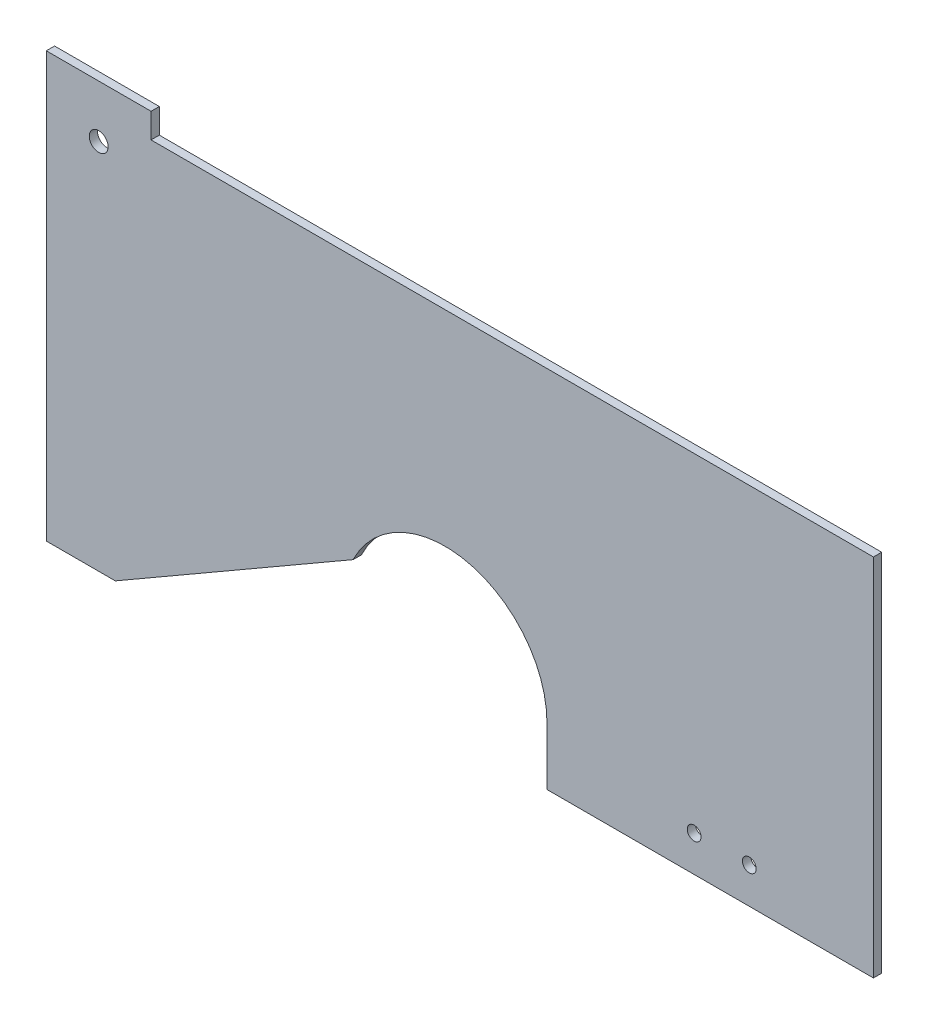
SolidWorks part; units mm, degrees
ref_plane "Front Plane" through (0, 0, 0) normal (0, 0, 1) x (1, 0, 0)
ref_plane "Top Plane" through (0, 0, 0) normal (0, 1, 0) x (1, 0, 0)
ref_plane "Right Plane" through (0, 0, 0) normal (1, 0, 0) x (0, 0, -1)
sketch "Sketch2" plane through (0, 0, 0) normal (0, 0, 1) x (1, 0, 0)
  line L0 (25.0304, 0) -> (111.2865, 49.8)
  line L1 (0, 0) -> (25.0304, 0)
  line L2 (0, 0) -> (0, 154)
  line L4 (300, 0) -> (300, 145)
  line L5 (181.6, 33.7) -> (181.6, 0)
  line L6 (181.6, 0) -> (300, 0)
  line L7 (19, 135) -> (19, 164.3674) construction
  line L11 (38, 145) -> (300, 145)
  line L12 (0, 154) -> (19, 154)
  line L13 (19, 154) -> (38, 154)
  line L14 (38, 154) -> (38, 145)
  line L15 (19, 135) -> (50019, 135) construction
  line L20 (19, 135) -> (19, -49865) construction
  circle A0 centre (19, 135) radius 3.425
  arc A1 (181.6, 33.7) -> (111.2865, 49.8) centre (144.6, 33.7) ccw
  point P19 (19, 154)
  dimension "D3" = 135
  dimension "D4" = 19
  dimension "D5" = 6.85
  dimension "D6" = 74
  dimension "D7" = 155.4
  dimension "D8" = 33.7
  dimension "D1" = 300
  dimension "D2" = 154
  dimension "D9" = 30
  dimension "D10" = 99.6
  dimension "D11" = 19
extrude "Boss-Extrude2" add sketch "Sketch2" along normal blind 3
sketch "Sketch3" plane through (0, 0, 3) normal (0, 0, 1) x (1, 0, 0)
  line L0 (300, 0) -> (300, 145) construction
  line L1 (181.6, 0) -> (300, 0)
  line L2 (181.6, 0) -> (181.6, 12.75)
  line L3 (181.6, 12.75) -> (300, 12.75)
  line L4 (300, 0) -> (300, 12.75)
  dimension "D1" = 12.75
extrude "Cut-Extrude1" cut sketch "Sketch3" against normal through all
sketch "Sketch4" plane through (0, 0, 3) normal (0, 0, 1) x (1, 0, 0)
  line L0 (19, 135) -> (19, -49865) construction
  line L1 (19, 135) -> (-49981, 135) construction
sketch "Sketch5" plane through (0, 0, 3) normal (0, 0, 1) x (1, 0, 0)
  line L0 (300, 12.75) -> (300, 145) construction
  line L1 (300, 12.75) -> (181.6, 12.75) construction
  circle A0 centre (254.98, 25.75) radius 2.5
  circle A1 centre (234.98, 25.75) radius 2.5
  dimension "D1" = 5
  dimension "D2" = 45.02
  dimension "D3" = 13
  dimension "D4" = 5
  dimension "D5" = 20
  dimension "D6" = 13
extrude "Cut-Extrude2" cut sketch "Sketch5" against normal through all
